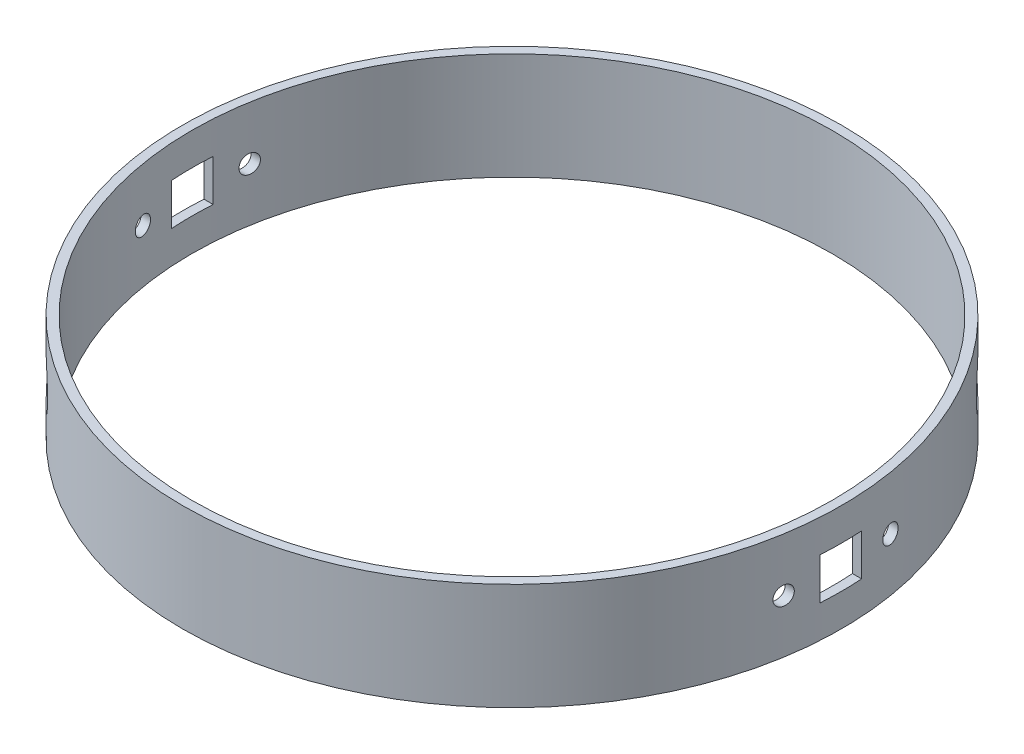
SolidWorks part; units mm, degrees
material "A-Glass Fiber"
ref_plane "Front Plane" through (0, 0, 0) normal (0, 0, 1) x (1, 0, 0)
ref_plane "Top Plane" through (0, 0, 0) normal (0, 1, 0) x (1, 0, 0)
ref_plane "Right Plane" through (0, 0, 0) normal (1, 0, 0) x (0, 0, -1)
sketch "Sketch1" plane through (0, 0, 0) normal (0, 1, 0) x (1, 0, 0)
  circle A0 centre (0, 0) radius 78.359
  circle A1 centre (0, 0) radius 76.1746
  dimension "D1" = 156.718
  dimension "D2" = 152.3492
extrude "Boss-Extrude1" add sketch "Sketch1" along normal blind 25.4
sketch "Sketch2" plane through (0, 0, 0) normal (1, 0, 0) x (0, 0, -1)
  line L0 (-78.359, 0) -> (78.359, 0) construction
  line L7 (0, 12.7) -> (0, 14.52) construction
  line L12 (4.953, 7.747) -> (-4.953, 7.747)
  line L13 (0, 25.4) -> (0, 0) construction
  line L14 (76.1746, 25.4) -> (-76.1746, 25.4) construction
  line L15 (-78.359, 0) -> (78.359, 0)
  line L16 (76.1746, 25.4) -> (-76.1746, 25.4)
  line L17 (-28.7231, 12.7) -> (26.1298, 12.7) construction
  line L25 (4.953, 7.747) -> (4.953, 17.653)
  line L26 (4.953, 17.653) -> (-4.953, 17.653)
  line L27 (-4.953, 7.747) -> (-4.953, 17.653)
  line L28 (4.953, 7.747) -> (-4.953, 17.653) construction
  line L29 (4.953, 17.653) -> (-4.953, 7.747) construction
  circle A0 centre (-12.7, 12.7) radius 2.1831
  circle A1 centre (12.7, 12.7) radius 2.1831
  point P0 (0, 9.85)
  point P14 (0, 3.175)
  point P27 (0, 12.7)
  dimension "D4" = 9.906
  dimension "D8" = 4.3663
  dimension "D1" = 12.7
  dimension "D5" = 9.906
extrude "Cut-Extrude1" cut sketch "Sketch2" along normal through all both and the other way through all contours L25 L12 L27 L26 | A1 | A0
ref_plane "Plane1" through (0, 0, 0) normal (0.9973, 0, 0.0728) x (0, -1, 0)
ref_plane "Plane2" through (0, 12.7, 0) normal (0, 1, 0) x (1, 0, 0)
mirror "Mirror2" about plane through (0, 0, 0) normal (1, 0, 0) of "Cut-Extrude1", "Boss-Extrude1" second plane through (0, 12.7, 0) second plane normal (0, 1, 0)
ref_plane "Plane3" through (0, 0, 0) normal (0.7071, 0, -0.7071) x (-0.7071, 0, -0.7071)
sketch "Sketch3" plane through (0, 0, 0) normal (0.7071, 0, -0.7071) x (-0.7071, 0, -0.7071)
  line L0 (0, 25.4) -> (0, 0) construction
  line L1 (-78.359, 0) -> (78.359, 0) construction
  circle A0 centre (0, 12.7) radius 6.35
  dimension "D1" = 12.7
  dimension "D2" = 12.7
extrude "Cut-Extrude2" cut sketch "Sketch3" against normal through all both and the other way through all
equation "\"Bodytube_OD\" = 6.17in"
equation "\"Bodytube_ID\" = 5.998in"
equation "\"D1@Sketch1\"=\"Bodytube_OD\""
equation "\"D2@Sketch1\"= \"Bodytube_ID\""
equation "\"Camera_Cutout_Width\"=10mm"
equation "\"Camera_Cutout_Height\"=7mm"
equation "\"Fwd_Tube_Length\" = 40in"
equation "\"BKHD_Screw_Diam\"= 3.5mm"
equation "\"Fwd_BKHD_From_Top\" = 18in"
equation "\"Shear_Screw_Diameter\" = 0.086in"
equation "\"Shear_Screw_Coupler_Location\" = 4.5in"
equation "\"Motor_OD\" = 4in"
equation "\"Mid_Coupler_Length\" = 13in"
equation "\"Aft_Section_Length\"= 36in"
equation "\"AB_Coupler_OD_Length\"= 1in"
equation "\"AB_Coupling_Section_Length\"= 0.375in"
equation "\"AB_Coupler_Length\"= \"AB_Coupler_OD_Length\" + \"AB_Coupling_Section_Length\" * 2"
equation "\"Cutout_Angle\" = 80"
equation "\"AB_Paddle_Height\" = 0.375in"
equation "\"AB_Coupler_Num_Screws\"= 4"
equation "\"AB_BKHD_Thickness\" = 0.375in"
equation "\"AB_Mount_From_Bottom\" = 23.175in"
equation "\"Num_Cutouts\" = 3"
equation "\"AB_Coupler_OD\"= 6.17in"
equation "\"AB_Coupler_ID\"= 5.75in"
equation "\"AB_Coupler_Surface_Diameter\"= 5.998in"
equation "\"AB_Coupling_Screw_Diameter\"= 0.15748in"
equation "\"AB_Central_Bushing_Length\" = .4724in"
equation "\"Lead_Screw_Dist\" = 3.4in"
equation "\"Lead_Screw_Diam\" = 0.386in"
equation "\"Lead_Screw_Length\" = (\"Mid_Coupler_Length\" + 2*0.375in + 2*.75in)"
equation "\"Paddle_Pin_Offset\" = .25in"
equation "\"Paddle_Pin_Radius\" = 2.25in"
equation "\"SS_Paddle_Pin_Radius\" = 2.25*0.66in"
equation "\"Paddle_Gear_OD\" = 3.2in"
equation "\"Drive_Gear_OD\" = 1.7in"
equation "\"Fin_Thickness\"= .118in"
equation "\"Guiderail_Cutout_Diameter\"= 1.5in"
equation "\"DB9_Hole_Dist\" = 25mm"
equation "\"DB9_Relief_Width\" = 0.47in"
equation "\"DB9_Relief_Hole_Offset\" = 0.09in"
equation "\"Airbrakes_Wire_Hole_Dia\" = .25in"
equation "\"Airbrakes_Wire_Hole_Dist\" = 1.1in"
equation "\"Servo_Gear_Offset\" = 0.5in"
equation "\"FWD_Shear_Screw_Dist\" = 1.5in"
equation "\"Camera_Screw_Dia\" = 0.216535"
equation "\"Camera_Hole_Angle\" = atn ( 2 / 3 * tan ( 12.5deg ) )"
equation "\"Coupler_OD\" = 5.998"
equation "\"Coupler_ID\" = 5.8"
equation "\"Mounting_Bracket_Centerhole_DIA\" = 0.4in"
equation "\"Drive_Gear_Shaft_DIA\" = \"Mounting_Bracket_Centerhole_DIA\" - 0.02in"
equation "\"Drive_Gear_Fillet\" = 0.22in"
equation "\"Drive_Gear_ID\" = 0.62in"
equation "\"Drive_Gear_Offset\" = 0.01in"
